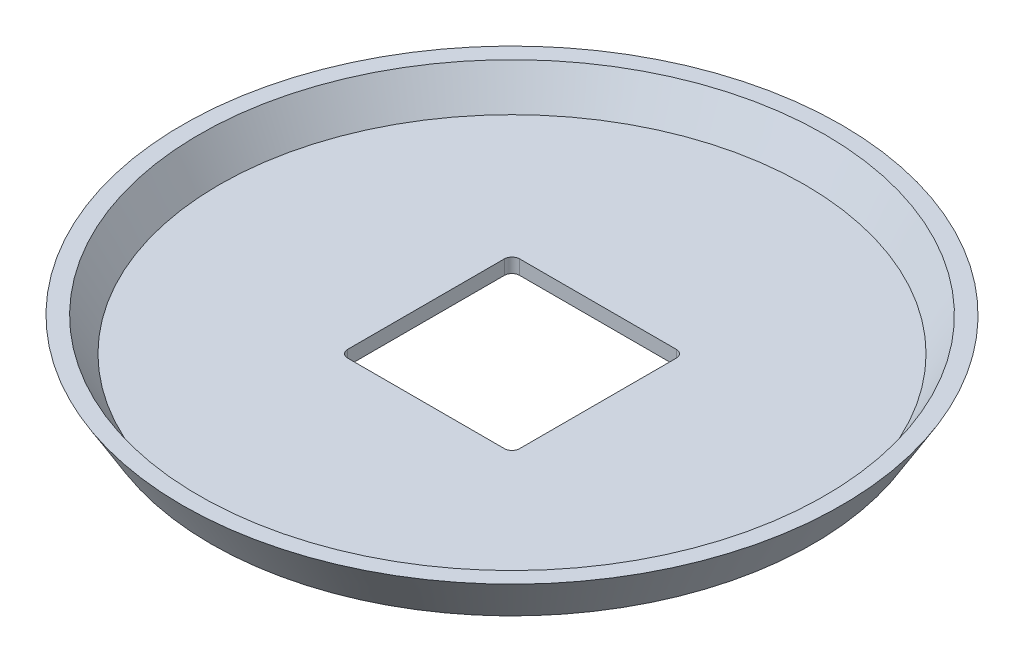
SolidWorks part; units mm, degrees
ref_plane "Front Plane" through (0, 0, 0) normal (0, 0, 1) x (1, 0, 0)
ref_plane "Top Plane" through (0, 0, 0) normal (0, 1, 0) x (1, 0, 0)
ref_plane "Right Plane" through (0, 0, 0) normal (1, 0, 0) x (0, 0, -1)
sketch "Sketch1" plane through (0, 0, 0) normal (0, 0, 1) x (1, 0, 0)
  line L0 (0, 0) -> (63, 0)
  line L1 (63, 0) -> (69, 10)
  line L6 (0, 3) -> (61.3014, 3)
  line L7 (61.3014, 3) -> (65.5014, 10)
  line L8 (69, 10) -> (65.5014, 10)
  line L9 (0, 0) -> (0, 3)
  line L10 (61.3014, 3) -> (66.4275, 11.5435) construction
  dimension "D1" = 69
  dimension "D2" = 63
  dimension "D3" = 10
  dimension "D4" = 3
revolve "Revolve1" add sketch "Sketch1" angle 360 about L9
sketch "Sketch2" plane through (0, 3, 0) normal (0, 1, 0) x (1, 0, 0)
  line L1 (-18, 18) -> (18, 18)
  line L2 (-18, 18) -> (-18, -18)
  line L3 (-18, -18) -> (18, -18)
  line L4 (18, 18) -> (18, -18)
  line L5 (-18, 18) -> (18, -18) construction
  line L6 (-18, -18) -> (18, 18) construction
  point P0 (0, 0)
  dimension "D1" = 36
  dimension "D2" = 36
  dimension "D12" = 0
  dimension "D13" = 0
extrude "Cut-Extrude1" cut sketch "Sketch2" against normal through all
fillet "Fillet1" radius 1.6 4 edges at (18, 1.5, -18) (18, 1.5, 18) (-18, 1.5, 18) (-18, 1.5, -18)
